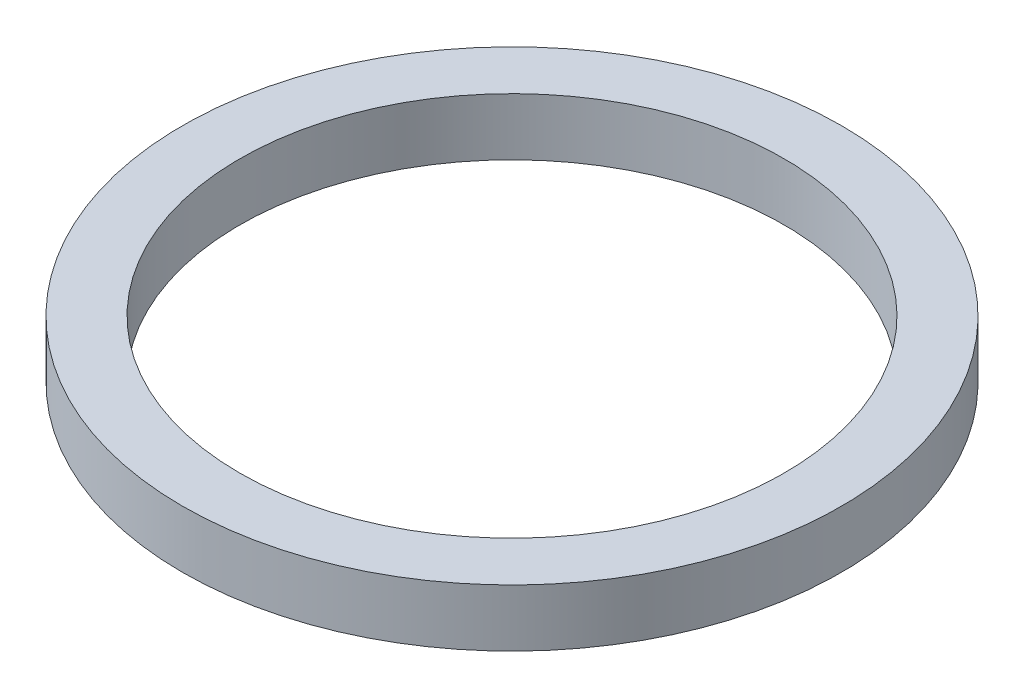
SolidWorks part; units mm, degrees
ref_plane "Front Plane" through (0, 0, 0) normal (0, 0, 1) x (1, 0, 0)
ref_plane "Top Plane" through (0, 0, 0) normal (0, 1, 0) x (1, 0, 0)
ref_plane "Right Plane" through (0, 0, 0) normal (1, 0, 0) x (0, 0, -1)
sketch "Sketch1" plane through (0, 0, 0) normal (0, 1, 0) x (1, 0, 0)
  circle A0 centre (0, 0) radius 57.5
  dimension "FLANGE_OD" = 115
extrude "Boss-Extrude1" add sketch "Sketch1" along normal blind 10
sketch "Sketch2" plane through (0, 0, 0) normal (0, 1, 0) x (1, 0, 0)
  circle A0 centre (0, 0) radius 47.5
  dimension "BORE_D" = 95
extrude "Cut-Extrude1" cut sketch "Sketch2" along normal through all
sketch "Sketch3" plane through (0, 10, 0) normal (0, 1, 0) x (1, 0, 0)
  circle A0 centre (0, 0) radius 26.9083 construction
  circle A1 centre (-26.9083, 0) radius 1.6914
  dimension "BOLT_D" = 3.3828
  dimension "BOLT_PCD" = 53.8166
extrude "Cut-Extrude2" cut sketch "Sketch3" against normal blind 6.6804 rebuild error yes
pattern_circular "CirPattern1" count 5 over 360 rebuild error yes
